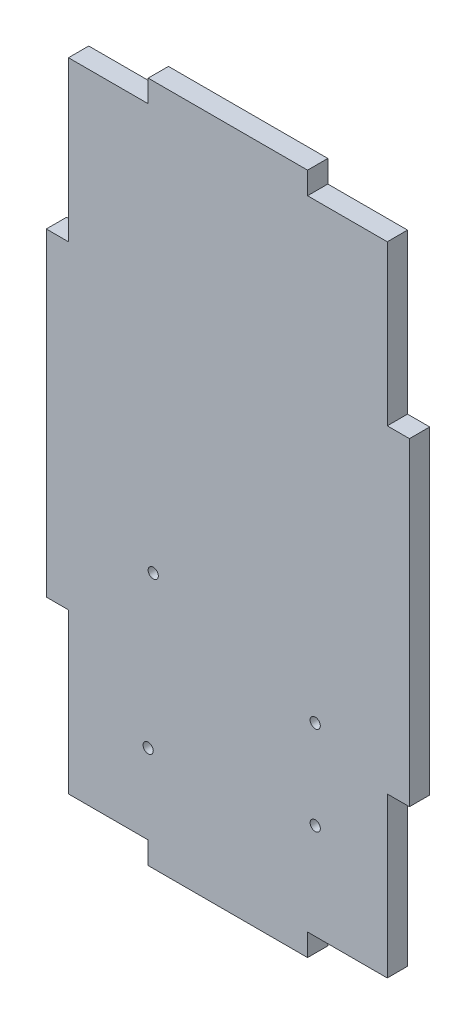
SolidWorks part; units mm, degrees
ref_plane "Front Plane" through (0, 0, 0) normal (0, 0, 1) x (1, 0, 0)
ref_plane "Top Plane" through (0, 0, 0) normal (0, 1, 0) x (1, 0, 0)
ref_plane "Right Plane" through (0, 0, 0) normal (1, 0, 0) x (0, 0, -1)
sketch "Sketch1" plane through (0, 0, 0) normal (0, 0, 1) x (1, 0, 0)
  line L1 (-50, 100) -> (50, 100)
  line L2 (-50, 100) -> (-50, -100)
  line L3 (-50, -100) -> (50, -100)
  line L4 (50, 100) -> (50, -100)
  line L5 (-50, 100) -> (50, -100) construction
  line L6 (-50, -100) -> (50, 100) construction
  point P0 (0, 0)
  dimension "D1" = 200
  dimension "D2" = 100
extrude "Boss-Extrude1" add sketch "Sketch1" along normal blind 6.36
sketch "Sketch2" [suppressed] plane through (0, 0, 3.36) normal (0, 0, 1) x (1, 0, 0)
  line L0 (50, 50) -> (-50, 50) construction
  line L1 (-25, 50) -> (25, 50)
  line L2 (-25, 50) -> (-25, 53.36)
  line L3 (-25, 53.36) -> (25, 53.36)
  line L4 (25, 50) -> (25, 53.36)
  line L5 (0, 0) -> (0, 53.36) construction
  line L6 (0, 0) -> (50, 0) construction
  line L7 (50, -50) -> (50, 50) construction
  dimension "D1" = 6.36
  dimension "D2" = 50
sketch "Sketch8" plane through (0, 0, 0) normal (0, 0, -1) x (-1, 0, 0)
  line L0 (0, 0) -> (0, 100) construction
  line L1 (-50, 100) -> (50, 100) construction
  line L2 (0, 0) -> (50, 0) construction
  line L3 (50, 100) -> (50, -100) construction
  line L5 (-25, 100) -> (25, 100)
  line L6 (-25, 100) -> (-25, 106.96)
  line L7 (-25, 106.96) -> (25, 106.96)
  line L8 (25, 100) -> (25, 106.96)
  dimension "D2" = 6.96
  dimension "D1" = 50
extrude "Boss-Extrude4" add sketch "Sketch8" against normal blind 6.36
mirror "Mirror4" about plane through (0, 0, 0) normal (0, 1, 0) of "Boss-Extrude4"
sketch "Sketch9" plane through (0, 0, 0) normal (0, 0, -1) x (-1, 0, 0)
  line L0 (0, 0) -> (50, 0) construction
  line L1 (50, 100) -> (50, -100) construction
  line L3 (50, 50) -> (56.96, 50)
  line L4 (50, 50) -> (50, -50)
  line L5 (50, -50) -> (56.96, -50)
  line L6 (56.96, 50) -> (56.96, -50)
  dimension "D1" = 100
  dimension "D2" = 6.96
extrude "Boss-Extrude5" add sketch "Sketch9" against normal blind 6.36
mirror "Mirror5" about plane through (0, 0, 0) normal (1, 0, 0) of "Boss-Extrude5"
sketch "Sketch10" plane through (0, 0, 6.36) normal (0, 0, 1) x (1, 0, 0)
  line L0 (0, 0) -> (0, 50) construction
  line L1 (50, 100) -> (25, 100) construction
  line L3 (-22.1665, 100) -> (22.1665, 100)
  line L4 (-22.1665, 100) -> (-22.1665, 90.4825)
  line L5 (-22.1665, 90.4825) -> (22.1665, 90.4825)
  line L6 (22.1665, 100) -> (22.1665, 90.4825)
  dimension "D1" = 9.5175
  dimension "D2" = 44.3329
extrude "Cut-Extrude1" [suppressed] cut sketch "Sketch10" against normal through all and the other way through all
mirror "Mirror6" [suppressed] about plane through (0, 0, 0) normal (0, 1, 0)
sketch "Sketch11" plane through (0, 0, 6.36) normal (0, 0, 1) x (1, 0, 0)
  line L0 (0, 0) -> (50, 0) construction
  line L1 (50, -100) -> (50, -50) construction
  line L3 (50, 18.3322) -> (46.2005, 18.3322)
  line L4 (50, 18.3322) -> (50, -18.3322)
  line L5 (50, -18.3322) -> (46.2005, -18.3322)
  line L6 (46.2005, 18.3322) -> (46.2005, -18.3322)
  dimension "D1" = 3.7995
  dimension "D2" = 36.6643
extrude "Cut-Extrude2" [suppressed] cut sketch "Sketch11" against normal through all and the other way through all
mirror "Mirror7" [suppressed] about plane through (0, 0, 0) normal (1, 0, 0)
sketch "Sketch12" plane through (0, 0, 6.36) normal (0, 0, 1) x (1, 0, 0)
  line L0 (-50, -50) -> (-50, -100) construction
  line L1 (-50, -100) -> (-25, -100) construction
  line L2 (-25, -75) -> (-25, -26.7) construction
  line L3 (27.4, -42) -> (27.4, -69.9) construction
  circle A0 centre (-25, -75) radius 1.6
  circle A1 centre (-23.4, -26.7) radius 1.6
  circle A2 centre (27.4, -69.9) radius 1.6
  circle A3 centre (27.4, -42) radius 1.6
  dimension "D1" = 3.2
  dimension "D2" = 25
  dimension "D3" = 25
  dimension "D5" = 48.3
  dimension "D7" = 5.1
  dimension "D9" = 50.8
  dimension "D10" = 27.9
extrude "arduino holes" cut sketch "Sketch12" against normal through all and the other way through all
sketch "Sketch13" plane through (0, 0, 6.36) normal (0, 0, 1) x (1, 0, 0)
  line L0 (25.9457, -65) -> (-18.2265, -65) construction
  line L1 (50, -100) -> (50, -50) construction
  line L2 (25, -100) -> (50, -100) construction
  circle A0 centre (25.9457, -65) radius 2
  circle A1 centre (-16.3351, -43.7788) radius 2
  circle A2 centre (-16.3351, -86.2212) radius 2
  dimension "D1" = 4
  dimension "D2" = 42.4424
  dimension "D3" = 42.2808
  dimension "D4" = 24.0543
  dimension "D5" = 35
extrude "battery holes" [suppressed] cut sketch "Sketch13" against normal blind 10
sketch "Sketch14" [suppressed] plane through (0, 0, 0) normal (0, 0, -1) x (-1, 0, 0)
  line L6 (33.2, -18.84) -> (45.2, -18.84)
  line L8 (45.2, -29.34) -> (33.2, -29.34)
  line L9 (45.2, -18.84) -> (45.2, -29.34)
  line L10 (33.2, -29.34) -> (33.2, -18.84)
  line L52 (50, -44.24) -> (50, -50)
  line L53 (50, -50) -> (100, -50)
  line L54 (100, -50) -> (100, -25)
  line L55 (100, -25) -> (106.96, -25)
  line L56 (106.96, -25) -> (106.96, 25)
  line L57 (106.96, 25) -> (100, 25)
  line L58 (100, 25) -> (100, 50)
  line L59 (100, 50) -> (50, 50)
  line L60 (50, 50) -> (50, 44.24)
  line L61 (50, 44.24) -> (-50, 44.24)
  line L62 (-50, 44.24) -> (-50, 50)
  line L63 (-50, 50) -> (-100, 50)
  line L64 (-100, 50) -> (-100, 25)
  line L65 (-100, 25) -> (-106.96, 25)
  line L66 (-106.96, 25) -> (-106.96, -25)
  line L67 (-106.96, -25) -> (-100, -25)
  line L68 (-100, -25) -> (-100, -50)
  line L69 (-100, -50) -> (-50, -50)
  line L70 (-50, -50) -> (-50, -44.24)
  line L71 (-50, -44.24) -> (50, -44.24)
  point P0 (-100, 50)
extrude "Cut-Extrude6" [suppressed] cut sketch "Sketch14" against normal through all contours L10 L8 L9 L6
sketch "Sketch15" [suppressed] plane through (0, 0, 0) normal (0, 0, -1) x (-1, 0, 0)
  line L0 (50.6, 25) -> (50.6, -25) construction
  line L1 (27.42, 19.24) -> (30.6, 19.24)
  line L2 (27.42, 19.24) -> (27.42, 6.74)
  line L3 (27.42, 6.74) -> (30.6, 6.74)
  line L4 (30.6, 19.24) -> (30.6, 6.74)
  line L5 (25, 44.24) -> (-25, 44.24) construction
  dimension "D1" = 12.5
  dimension "D2" = 3.18
  dimension "D3" = 20
  dimension "D4" = 25
extrude "Cut-Extrude7" [suppressed] cut sketch "Sketch15" against normal blind 10
equation "\"Sheet Thickness\"= 6.36mm"
equation "\"Height\"= 100mm"
equation "\"Length\"= 200mm"
equation "\"Width\"= 100mm"
equation "\"D1@Boss-Extrude1\"=\"Sheet Thickness\""
equation "\"D1@Sketch2\"=\"Sheet Thickness\""
equation "\"D2@Sketch2\"=\"Height\"/2"
equation "\"Kerf\"= .60mm"
equation "\"D2@Sketch9\"=\"Sheet Thickness\"+\"Kerf\""
equation "\"D1@Sketch9\"     = \"Length\"/2"
equation "\"D2@Sketch8\"=\"Sheet Thickness\"+\"Kerf\""
equation "\"D1@Sketch10\"=\"Sheet Thickness\"-\"Kerf\""
equation "\"D2@Sketch10\"    = \"Width\"/2"
equation "\"D1@Sketch11\"=\"Sheet Thickness\"-\"Kerf\""
equation "\"D2@Sketch11\"=\"Height\"/2"
